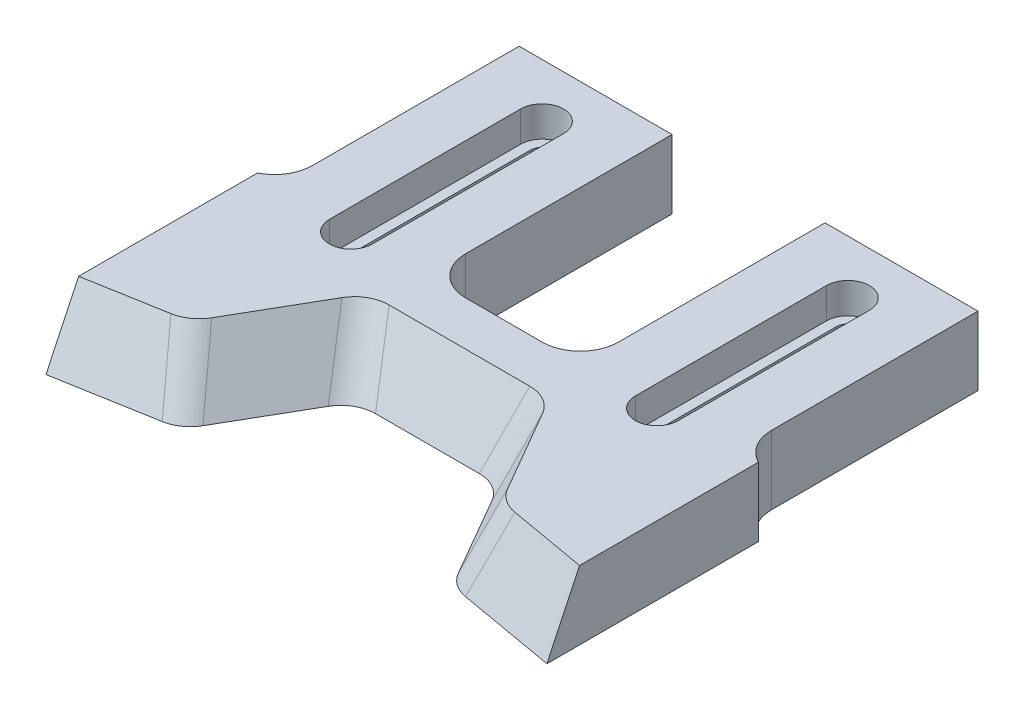
SolidWorks part; units mm, degrees
material "POM Acetal Copolymer"
ref_plane "Front Plane" through (0, 0, 0) normal (0, 0, 1) x (1, 0, 0)
ref_plane "Top Plane" through (0, 0, 0) normal (0, 1, 0) x (1, 0, 0)
ref_plane "Right Plane" through (0, 0, 0) normal (1, 0, 0) x (0, 0, -1)
sketch "Sketch1" plane through (0, 0, 0) normal (0, 1, 0) x (1, 0, 0)
  line L0 (0, 0) -> (0, 60)
  line L1 (0, 60) -> (75.5, 60)
  line L2 (75.5, 60) -> (75.5, 0)
  line L3 (75.5, 0) -> (55.5, 3.5265)
  line L4 (20, 3.5265) -> (0, 0)
  line L5 (20, 3.5265) -> (28.3563, 18)
  line L6 (28.3563, 18) -> (47.1437, 18)
  line L7 (47.1437, 18) -> (55.5, 3.5265)
  dimension "D1" = 60
  dimension "D2" = 80
  dimension "D3" = 75.5
  dimension "D4" = 30
  dimension "D5" = 18
  dimension "D6" = 20
extrude "Boss-Extrude1" add sketch "Sketch1" along normal blind 9
sketch "Sketch4" plane through (0, 9, 0) normal (0, 1, 0) x (1, 0, 0)
  line L0 (17.75, 53) -> (17.75, 28) construction
  line L1 (19.25, 53) -> (19.25, 28)
  line L2 (16.25, 53) -> (16.25, 28)
  line L3 (57.75, 53) -> (57.75, 28) construction
  line L4 (59.25, 53) -> (59.25, 28)
  line L5 (56.25, 53) -> (56.25, 28)
  line L6 (75.5, 60) -> (0, 60) construction
  line L9 (75.5, 60) -> (0, 60) construction
  arc A0 (19.25, 53) -> (16.25, 53) centre (17.75, 53) ccw
  arc A1 (16.25, 28) -> (19.25, 28) centre (17.75, 28) ccw
  arc A2 (59.25, 53) -> (56.25, 53) centre (57.75, 53) ccw
  arc A3 (56.25, 28) -> (59.25, 28) centre (57.75, 28) ccw
  point P2 (17.75, 40.5)
  point P7 (57.75, 40.5)
  point P14 (37.75, 60)
  dimension "D1" = 3
  dimension "D2" = 3
  dimension "D3" = 40
  dimension "D4" = 20
  dimension "D5" = 25
  dimension "D6" = 7
extrude "Cut-Extrude2" cut sketch "Sketch4" against normal up to next
sketch "Sketch5" plane through (0, 9, 0) normal (0, 1, 0) x (1, 0, 0)
  line L0 (75.5, 60) -> (0, 60) construction
  line L1 (27.75, 60) -> (47.75, 60)
  line L2 (27.75, 60) -> (27.75, 28)
  line L3 (27.75, 28) -> (47.75, 28)
  line L4 (47.75, 60) -> (47.75, 28)
  line L7 (67.75, 60) -> (75.5, 60)
  line L8 (0, 60) -> (7.75, 60)
  line L9 (0, 60) -> (0, 28)
  line L10 (0, 28) -> (7.75, 28)
  line L11 (7.75, 60) -> (7.75, 28)
  line L12 (67.75, 60) -> (67.75, 28)
  line L13 (67.75, 28) -> (75.5, 28)
  line L14 (75.5, 60) -> (75.5, 28)
  arc A0 (19.25, 53) -> (16.25, 53) centre (17.75, 53) ccw construction
  arc A1 (59.25, 53) -> (56.25, 53) centre (57.75, 53) ccw construction
  point P6 (17.75, 54.5)
  point P21 (57.75, 54.5)
  dimension "D1" = 20
  dimension "D2" = 20
  dimension "D3" = 32
  dimension "D4" = 10
  dimension "D5" = 10
extrude "Cut-Extrude3" cut sketch "Sketch5" against normal blind 10
fillet "Fillet1" radius 5 4 edges at (67.75, 4.5, -28) (47.75, 4.5, -28) (27.75, 4.5, -28) (7.75, 4.5, -28)
sketch "Sketch6" plane through (0, 9, 0) normal (0, 1, 0) x (1, 0, 0)
  line L0 (17.75, 53) -> (17.75, 28) construction
  line L1 (20.55, 53) -> (20.55, 28)
  line L2 (14.95, 53) -> (14.95, 28)
  line L3 (57.75, 53) -> (57.75, 28) construction
  line L4 (60.55, 53) -> (60.55, 28)
  line L5 (54.95, 53) -> (54.95, 28)
  arc A0 (20.55, 53) -> (14.95, 53) centre (17.75, 53) ccw
  arc A1 (14.95, 28) -> (20.55, 28) centre (17.75, 28) ccw
  arc A2 (60.55, 53) -> (54.95, 53) centre (57.75, 53) ccw
  arc A3 (54.95, 28) -> (60.55, 28) centre (57.75, 28) ccw
  point P4 (17.75, 40.5)
  point P9 (57.75, 40.5)
  dimension "D1" = 5.6
  dimension "D2" = 5.6
extrude "Cut-Extrude4" cut sketch "Sketch6" against normal blind 4
chamfer "Chamfer1" distance 9 angle 25 5 edges at (65.5, 9, -1.7633) (10, 9, -1.7633) (51.3219, 9, -10.7633) (37.75, 9, -18) (24.1781, 9, -10.7633) first distance on face at (65.5, 4.5, -1.7633) first distance on face at (10, 4.5, -1.7633) first distance on face at (51.3219, 4.5, -10.7633) first distance on face at (37.75, 4.5, -18) first distance on face at (24.1781, 4.5, -10.7633)
fillet "Fillet2" radius 5 4 edges at (56.828, 4.5, -5.4231) (48.3552, 4.5, -20.0984) (18.672, 4.5, -5.4231) (27.1448, 4.5, -20.0984)
sketch "Sketch7" plane through (0, 9, 0) normal (0, 1, 0) x (1, 0, 0)
  line L1 (0, 0) -> (5, 0)
  line L2 (0, 0) -> (0, 33.0851)
  line L3 (0, 33.0851) -> (5, 33.0851)
  line L4 (5, 0) -> (5, 33.0851)
  line L5 (75.5, 0) -> (70.5, 0)
  line L6 (75.5, 0) -> (75.5, 33.7453)
  line L7 (75.5, 33.7453) -> (70.5, 33.7453)
  line L8 (70.5, 0) -> (70.5, 33.7453)
  dimension "D1" = 5
extrude "Cut-Extrude5" cut sketch "Sketch7" against normal up to next
